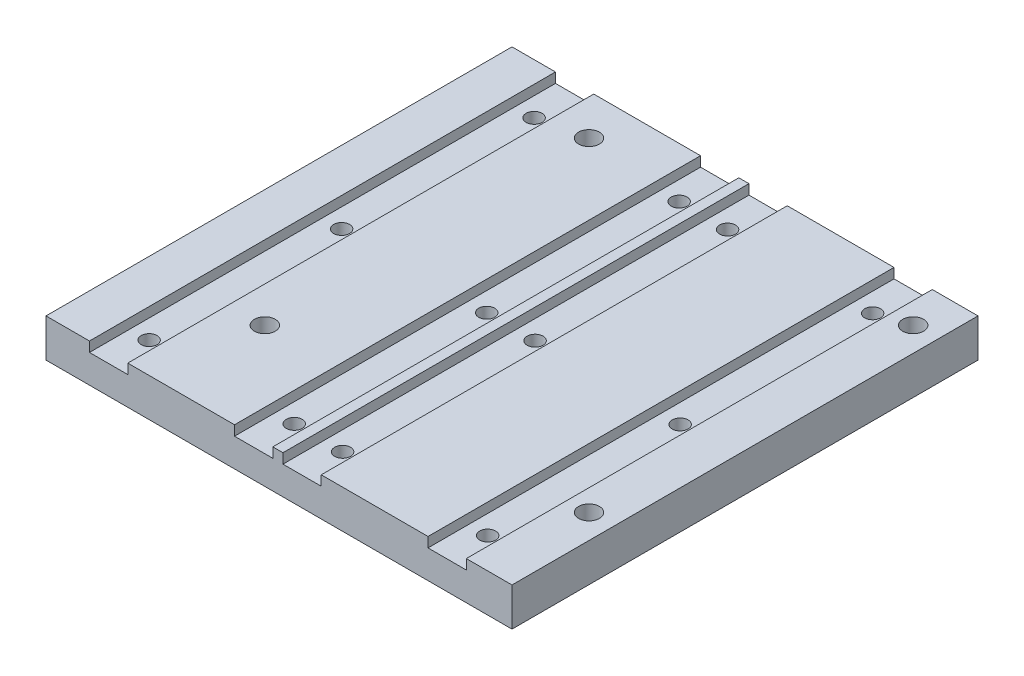
SolidWorks part; units mm, degrees
material "Acrylic (Medium-high impact)"
ref_plane "Front Plane" through (0, 0, 0) normal (0, 0, 1) x (1, 0, 0)
ref_plane "Top Plane" through (0, 0, 0) normal (0, 1, 0) x (1, 0, 0)
ref_plane "Right Plane" through (0, 0, 0) normal (1, 0, 0) x (0, 0, -1)
sketch "Sketch1" plane through (0, 0, 0) normal (0, 1, 0) x (1, 0, 0)
  line L1 (73.025, 73.025) -> (-73.025, 73.025)
  line L2 (73.025, 73.025) -> (73.025, -73.025)
  line L3 (73.025, -73.025) -> (-73.025, -73.025)
  line L4 (-73.025, 73.025) -> (-73.025, -73.025)
  line L5 (73.025, 73.025) -> (-73.025, -73.025) construction
  line L6 (73.025, -73.025) -> (-73.025, 73.025) construction
  line L7 (-36.195, 60.325) -> (65.405, 60.325) construction
  line L8 (-36.195, 60.325) -> (-36.195, -41.275) construction
  line L9 (-36.195, -41.275) -> (65.405, -41.275) construction
  line L10 (65.405, 60.325) -> (65.405, -41.275) construction
  line L11 (-36.195, 60.325) -> (65.405, -41.275) construction
  line L12 (-36.195, -41.275) -> (65.405, 60.325) construction
  point P0 (0, 0)
  point P6 (14.605, 9.525)
  dimension "D1" = 146.05
  dimension "D2" = 146.05
  dimension "D3" = 101.6
  dimension "D4" = 7.62
  dimension "D5" = 12.7
extrude "Boss-Extrude1" add sketch "Sketch1" against normal blind 12
hole_wizard "1/4 Clearance Hole1" positions "Sketch2" profile "Sketch3" hole size "1/4" standard "ANSI Inch" end condition through all
sketch "Sketch2" plane through (0, 0, 0) normal (0, 1, 0) x (1, 0, 0)
  point P0 (-36.195, 60.325)
  point P3 (-36.195, -41.275)
  point P6 (65.405, -41.275)
  point P9 (65.405, 60.325)
sketch "Sketch3" plane through (-36.195, 0, -60.325) normal (1, 0, 0) x (0, 0, 1)
  line L0 (0, 0) -> (0, 12)
  line L1 (0, 12) -> (3.2639, 12)
  line L2 (3.2639, 12) -> (3.2639, 0)
  line L5 (3.2639, 0) -> (0, 0)
  line L11 (0, -6.35) -> (0, 107.95) construction
  dimension "Thru Hole Dia." = 6.5278
  dimension "Thru Hole Depth" = 12
sketch "Sketch4" plane through (0, 0, 73.025) normal (0, 0, 1) x (1, 0, 0)
  line L0 (-73.025, 0) -> (73.025, 0) construction
  line L1 (46.705, -3.11) -> (58.705, -3.11)
  line L2 (46.705, -3.11) -> (46.705, 0)
  line L3 (46.705, 0) -> (58.705, 0)
  line L4 (58.705, -3.11) -> (58.705, 0)
  line L5 (46.705, -3.11) -> (58.705, 0) construction
  line L6 (46.705, 0) -> (58.705, -3.11) construction
  line L7 (73.025, -12) -> (73.025, 0) construction
  line L8 (-73.025, -12) -> (73.025, -12) construction
  point P0 (52.705, -1.555)
  dimension "D1" = 8.89
  dimension "D2" = 12
  dimension "D3" = 20.32
extrude "Cut-Extrude1" cut sketch "Sketch4" against normal through all
sketch "Sketch6" plane through (0, -12, 0) normal (0, -1, 0) x (1, 0, 0)
  line L0 (52.705, 60.325) -> (52.705, -60.325) construction
  line L1 (46.705, 73.025) -> (58.705, 73.025) construction
  line L2 (73.025, 73.025) -> (73.025, -73.025) construction
  line L3 (46.705, -73.025) -> (-73.025, -73.025) construction
  point P5 (52.705, 73.025)
  point P8 (73.025, 0)
  point P10 (52.705, 0)
  dimension "D1" = 12.7
hole_wizard "CBORE for #10 Socket Head Cap Screw1" positions "Sketch9" profile "Sketch8" counterbore size "#10" standard "ANSI Inch" end condition through all
sketch "Sketch9" plane through (0, -12, 0) normal (0, -1, 0) x (-1, 0, 0)
  point P0 (-52.705, -60.325)
  point P3 (-52.705, 60.325)
  point P7 (-52.705, 0)
sketch "Sketch8" plane through (52.705, -12, 60.325) normal (1, 0, 0) x (0, 0, -1)
  line L0 (0, 0) -> (0, 12)
  line L1 (0, 12) -> (2.4892, 12)
  line L3 (2.4892, 12) -> (2.4892, 5.08)
  line L4 (2.4892, 5.08) -> (4.7625, 5.08)
  line L5 (4.7625, 5.08) -> (4.7625, 0)
  line L7 (4.7625, 0) -> (0, 0)
  line L11 (0, -6.35) -> (0, 107.95) construction
  dimension "Thru Hole Dia." = 4.9784
  dimension "Thru Hole Depth" = 12
  dimension "C'Bore Dia." = 9.525
  dimension "C'Bore Depth" = 5.08
pattern_linear "LPattern1" count 2 spacing 45.466 along (-1, 0, 0) count 2 spacing 60.641 along (-1, 0, 0) of "Cut-Extrude1", "CBORE for #10 Socket Head Cap Screw1"
